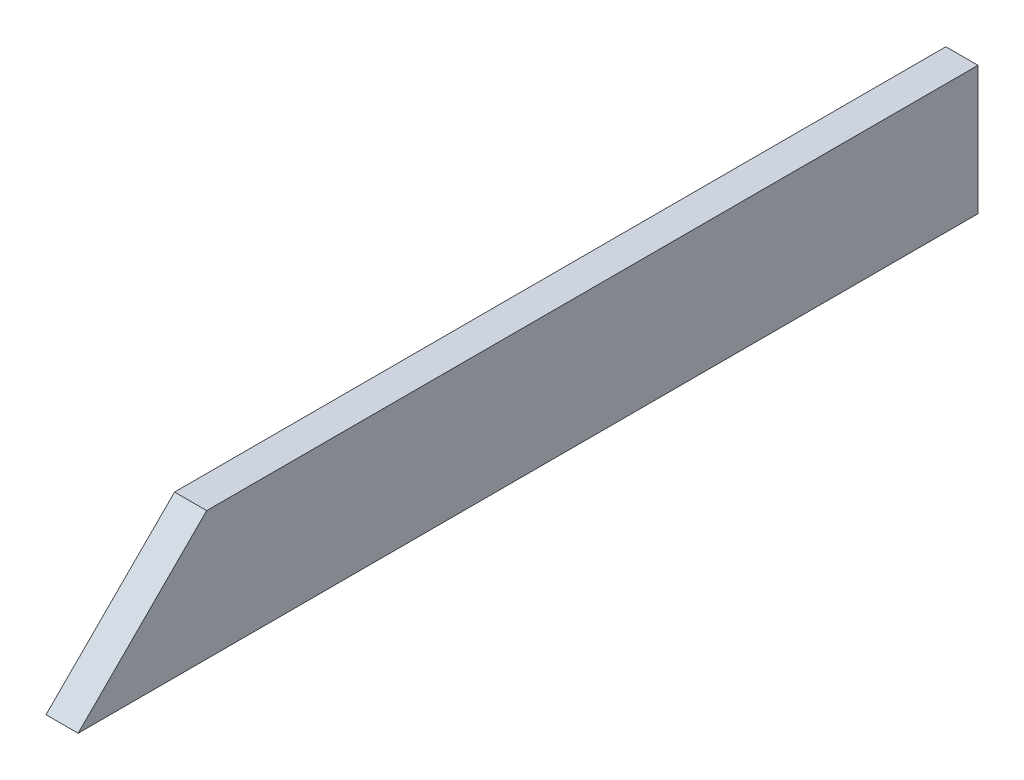
SolidWorks part; units mm, degrees
ref_plane "Front Plane" through (0, 0, 0) normal (0, 0, 1) x (1, 0, 0)
ref_plane "Top Plane" through (0, 0, 0) normal (0, 1, 0) x (1, 0, 0)
ref_plane "Right Plane" through (0, 0, 0) normal (1, 0, 0) x (0, 0, -1)
sketch "Sketch1" plane through (0, 0, 0) normal (1, 0, 0) x (0, 0, -1)
  line L1 (-177.8, -25.4) -> (177.8, -25.4)
  line L2 (-177.8, -25.4) -> (-177.8, 25.4)
  line L3 (-177.8, 25.4) -> (177.8, 25.4)
  line L4 (177.8, -25.4) -> (177.8, 25.4)
  line L5 (-177.8, -25.4) -> (177.8, 25.4) construction
  line L6 (-177.8, 25.4) -> (177.8, -25.4) construction
  point P0 (0, 0)
  dimension "D1" = 355.6
  dimension "D2" = 50.8
extrude "Boss-Extrude1" add sketch "Sketch1" along normal blind 12.7
sketch "Sketch2" plane through (12.7, 0, 0) normal (1, 0, 0) x (0, 0, -1)
  line L0 (-177.8, -25.4) -> (-127, 25.4)
  line L1 (177.8, 25.4) -> (-177.8, 25.4) construction
  dimension "D1" = 50.8
extrude "Cut-Extrude1" cut sketch "Sketch2" against normal through all and the other way through all
